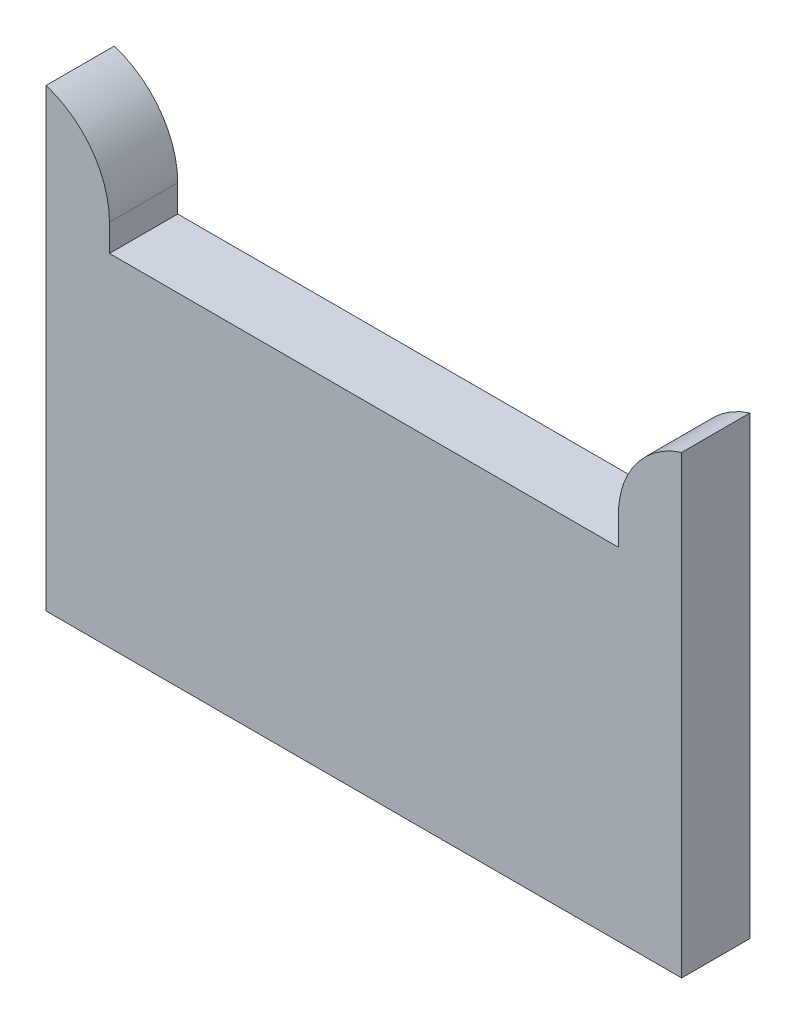
SolidWorks part; units mm, degrees
ref_plane "Front Plane" through (0, 0, 0) normal (0, 0, 1) x (1, 0, 0)
ref_plane "Top Plane" through (0, 0, 0) normal (0, 1, 0) x (1, 0, 0)
ref_plane "Right Plane" through (0, 0, 0) normal (1, 0, 0) x (0, 0, -1)
sketch "Sketch1" plane through (0, 0, 0) normal (0, 0, 1) x (1, 0, 0)
  line L0 (0, 36.6169) -> (0, -36.6169) construction
  line L1 (-27.9279, -36.6169) -> (27.9279, -36.6169)
  line L2 (27.9279, -36.6169) -> (27.9279, 3.3831)
  line L3 (27.9279, 3.3831) -> (22.3557, 3.3831)
  line L4 (22.3557, 3.3831) -> (22.3557, -6.6169)
  line L5 (22.3557, -6.6169) -> (-22.3557, -6.6169)
  line L6 (-27.9279, -36.6169) -> (-27.9279, 3.3831)
  line L7 (-22.3557, 3.3831) -> (-22.3557, -6.6169)
  line L8 (-27.9279, 3.3831) -> (-22.3557, 3.3831)
  point P12 (0, -6.6169)
  dimension "D1" = 40
  dimension "D2" = 30
extrude "Boss-Extrude1" add sketch "Sketch1" along normal blind 6
fillet "Fillet7" radius 8 1 edges at (-22.3557, 3.3831, 3)
fillet "Fillet8" radius 8 1 edges at (22.3557, 3.3831, 3)
